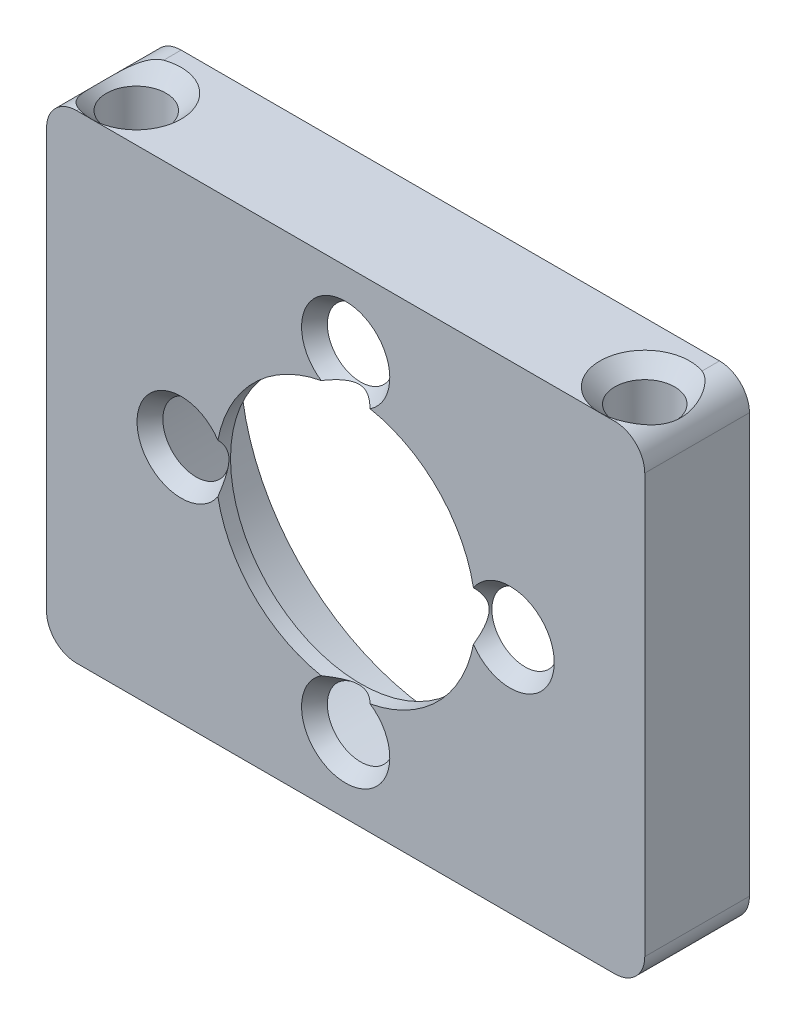
SolidWorks part; units mm, degrees
ref_plane "Front Plane" through (0, 0, 0) normal (0, 0, 1) x (1, 0, 0)
ref_plane "Top Plane" through (0, 0, 0) normal (0, 1, 0) x (1, 0, 0)
ref_plane "Right Plane" through (0, 0, 0) normal (1, 0, 0) x (0, 0, -1)
sketch "Sketch1" plane through (0, 0, 0) normal (0, 0, 1) x (1, 0, 0)
  line L1 (-20, 16) -> (20, 16)
  line L2 (-20, 16) -> (-20, -16)
  line L3 (-20, -16) -> (20, -16)
  line L4 (20, 16) -> (20, -16)
  line L5 (-20, 16) -> (20, -16) construction
  line L6 (-20, -16) -> (20, 16) construction
  point P0 (0, 0)
  dimension "D1" = 40
  dimension "D2" = 32
extrude "Boss-Extrude1" add sketch "Sketch1" along normal blind 7
sketch "Sketch2" plane through (0, 0, 0) normal (0, 0, -1) x (-1, 0, 0)
  circle A0 centre (0, 0) radius 14.05
  dimension "D1" = 28.1
extrude "Cut-Extrude1" cut sketch "Sketch2" against normal blind 6
sketch "Sketch3" plane through (0, 0, 6) normal (0, 0, -1) x (-1, 0, 0)
  circle A0 centre (0, 0) radius 8.7
  dimension "D1" = 17.4
extrude "Cut-Extrude2" cut sketch "Sketch3" against normal blind 6
sketch "Sketch4" plane through (0, 0, 6) normal (0, 0, -1) x (-1, 0, 0)
  circle A0 centre (0, 0) radius 11
  circle A1 centre (0, 11) radius 1.5
  circle A2 centre (11, 0) radius 1.5
  circle A3 centre (0, -11) radius 1.5
  circle A4 centre (-11, 0) radius 1.5
  point P14 (0, 0)
  dimension "D1" = 22
  dimension "D2" = 3
  dimension "D3" = 4
extrude "Cut-Extrude3" cut sketch "Sketch4" against normal blind 6 contours A3 | A4 | A2 | A1
chamfer "Chamfer1" distance 1.45 angle 54 4 edges at (1.5, -11, 7) (-9.5, 0, 7) (12.5, 0, 7) (1.5, 11, 7)
sketch "Sketch5" plane through (0, 16, 0) normal (0, 1, 0) x (1, 0, 0)
  line L0 (0, 0) -> (0, -4)
  line L1 (-17, -4) -> (17, -4)
  circle A0 centre (-17, -4) radius 2
  circle A1 centre (17, -4) radius 2
  point P6 (0, -4)
  dimension "D4" = 4
  dimension "D1" = 4
  dimension "D2" = 34
extrude "Cut-Extrude4" cut sketch "Sketch5" against normal through all both and the other way through all contours A1 | A0
fillet "Fillet1" radius 2 4 edges at (20, -16, 3.5) (-20, -16, 3.5) (-20, 16, 3.5) (20, 16, 3.5)
sketch "Sketch6" plane through (0, 16, 0) normal (0, 1, 0) x (1, 0, 0)
  circle A0 centre (-17, -4) radius 2.375
  circle A1 centre (17, -4) radius 2.375
  dimension "D1" = 4.75
extrude "Cut-Extrude5" cut sketch "Sketch6" against normal blind 5 from offset 5 offset against normal yes
mirror "Mirror1" about plane through (0, 0, 0) normal (0, 1, 0) of "Cut-Extrude5"
chamfer "Chamfer2" distance 1 angle 45 4 edges at (15, -16, 4) (-15, -16, 4) (-15, 16, 4) (15, 16, 4)
